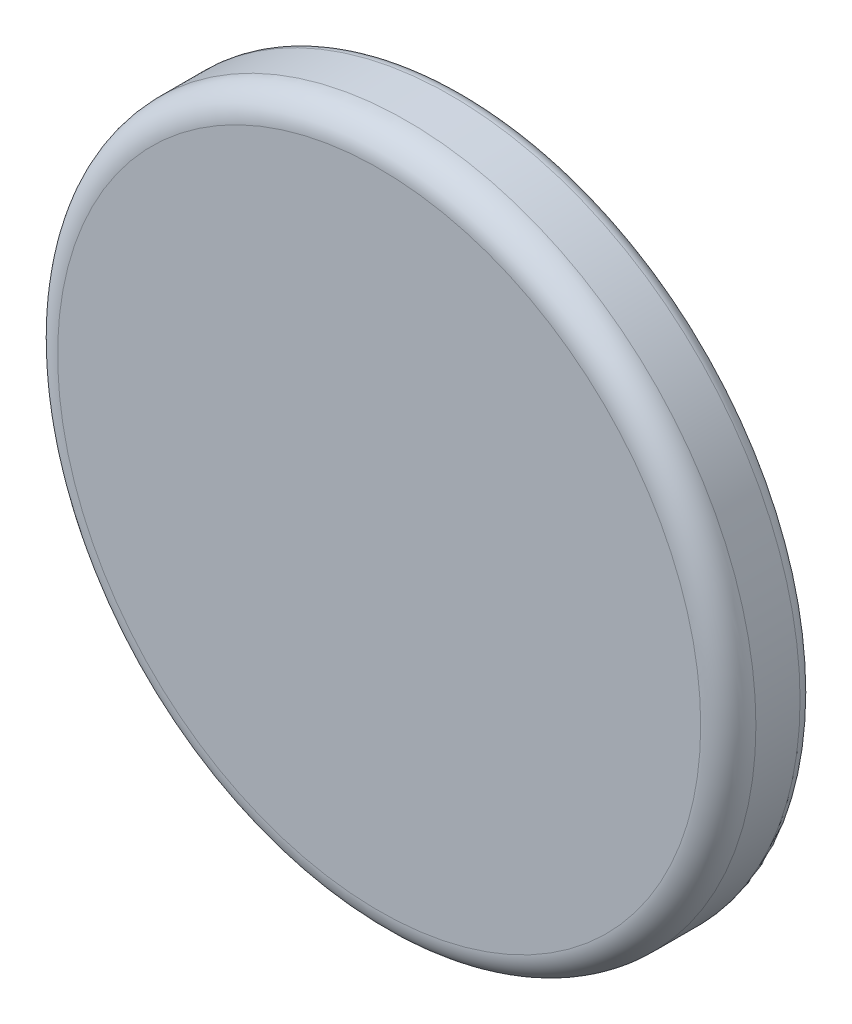
SolidWorks part; units mm, degrees
ref_plane "前视基准面" through (0, 0, 0) normal (0, 0, 1) x (1, 0, 0)
ref_plane "上视基准面" through (0, 0, 0) normal (0, 1, 0) x (1, 0, 0)
ref_plane "右视基准面" through (0, 0, 0) normal (1, 0, 0) x (0, 0, -1)
other "Configuration Table"
sketch "草图1" plane through (0, 0, 0) normal (0, 0, 1) x (1, 0, 0)
  line L0 (-2, 0) -> (2, 0) construction
  line L1 (0, -2) -> (0, 2) construction
  line L7 (-2, -0.55) -> (-2, 0.55)
  line L8 (0.55, 2) -> (-0.55, 2)
  line L12 (-2, 0.55) -> (-0.55, 0.55)
  line L13 (-0.55, 0.55) -> (-0.55, 2)
  line L14 (-2, -0.55) -> (-0.55, -0.55)
  line L17 (0.55, 2) -> (0.55, 0.55)
  line L18 (-0.55, -0.55) -> (0.55, 0.55) construction
  line L19 (2, 0.55) -> (0.55, 0.55)
  line L20 (2, 0.55) -> (2, -0.55)
  line L21 (0.55, -0.55) -> (2, -0.55)
  line L22 (-0.55, -2) -> (-0.55, -0.55)
  line L23 (-0.55, -2) -> (0.55, -2)
  line L24 (0.55, -2) -> (0.55, -0.55)
  circle A1 centre (0, 0) radius 2.4
  circle A3 centre (0, 0) radius 12.65
  circle A5 centre (0, 0) radius 11.65
  point P4 (0, 0)
  point P5 (0, 0)
  point P8 (0, 0)
  point P9 (0, 0)
  point P12 (-2, 0)
  point P15 (0, 2)
  point P22 (0, 0)
  dimension "D1" = 4.8
  dimension "D6" = 1.1
  dimension "D7" = 25.3
  dimension "D2" = 4
  dimension "D3" = 4
  dimension "D4" = 1.1
  dimension "D5" = 1.1
  dimension "D8" = 1.1
extrude "凸台-拉伸1" add sketch "草图1" against normal blind 2.1 contours A1 L24 L23 L22 L14 L7 L12 L13 L8 L17 L19 L20 L21 region at (-2.3321, 0, 0)
extrude "凸台-拉伸2" add sketch "草图1<9>" along normal blind 1 contours L23 L24 L21 L20 L19 L17 L8 L13 L12 L7 L14 L22 | A1 L24 L23 L22 L14 L7 L12 L13 L8 L17 L19 L20 L21 | A5 A1 region at (0, 0, 0) region at (-2.3321, 0, 0) region at (-11.3205, 0, 0)
sketch "草图1<9>" plane through (0, 0, 0) normal (0, 0, 1) x (1, 0, 0) same geometry as "草图1"
extrude "凸台-拉伸3" add sketch "草图1<10>" along normal blind 1 and the other way blind 2.1 contours A3 A5 region at (-12.2922, 0, 0)
sketch "草图1<10>" plane through (0, 0, 0) normal (0, 0, 1) x (1, 0, 0) same geometry as "草图1"
fillet "圆角1" radius 1 1 edges at (12.65, 0, 1)
fillet "圆角2" radius 0.5 1 edges at (11.65, 0, -2.1) type face fillet first side face at (11.65, 0, -2.1) second side face at (11.65, 0, -2.1)
fillet "圆角3" radius 0.5 1 edges at (12.65, 0, -2.1) type face fillet first side face at (12.65, 0, 0) second side face at (12.15, 0, -2.1)
fillet "圆角4" radius 1 1 edges at (11.65, 0, 0)
